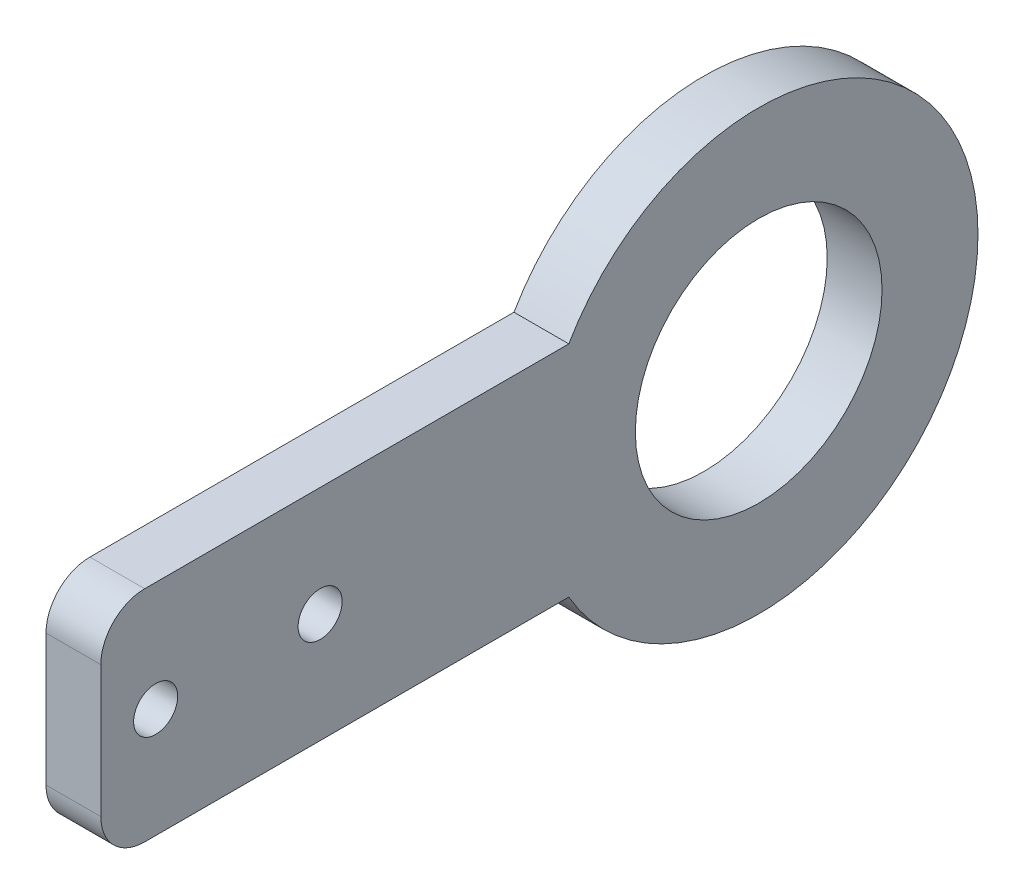
SolidWorks part; units mm, degrees
material "5052-O"
ref_plane "Front Plane" through (0, 0, 0) normal (0, 0, 1) x (1, 0, 0)
ref_plane "Top Plane" through (0, 0, 0) normal (0, 1, 0) x (1, 0, 0)
ref_plane "Right Plane" through (0, 0, 0) normal (1, 0, 0) x (0, 0, -1)
sketch "Sketch1" plane through (0, 0, 0) normal (1, 0, 0) x (0, 0, -1)
  line L1 (-44.45, -12.7) -> (44.45, -12.7)
  line L2 (-44.45, -12.7) -> (-44.45, 12.7)
  line L3 (-44.45, 12.7) -> (44.45, 12.7)
  line L4 (44.45, -12.7) -> (44.45, 12.7)
  line L5 (-44.45, -12.7) -> (44.45, 12.7) construction
  line L6 (-44.45, 12.7) -> (44.45, -12.7) construction
  point P0 (0, 0)
  dimension "D1" = 25.4
  dimension "D2" = 88.9
extrude "Boss-Extrude1" add sketch "Sketch1" along normal mid plane 6.35
fillet "Fillet1" radius 12.7 2 edges at (0, -12.7, -44.45) (0, 12.7, -44.45)
hole_wizard "#10 Clearance Hole1" positions "Sketch3" profile "Sketch5" hole size "#10" standard "ANSI Inch" end condition through all
sketch "Sketch3" plane through (3.175, 6.2729, 168.827) normal (1, 0, 0) x (0, 0, -1)
  line L0 (124.377, 6.4271) -> (124.377, -18.9729) construction
  point P0 (149.777, -6.2729)
  point P3 (130.727, -6.2729)
  point P8 (124.377, -6.2729)
  dimension "D1" = 19.05
  dimension "D2" = 6.35
sketch "Sketch5" plane through (3.175, 0, 19.05) normal (0, 1, 0) x (0, 0, -1)
  line L0 (0, 0) -> (0, 6.35)
  line L1 (0, 6.35) -> (2.5527, 6.35)
  line L2 (2.5527, 6.35) -> (2.5527, 0)
  line L5 (2.5527, 0) -> (0, 0)
  line L11 (0, -6.35) -> (0, 107.95) construction
  dimension "Thru Hole Dia." = 5.1054
  dimension "Thru Hole Depth" = 6.35
fillet "Fillet2" radius 5.08 2 edges at (0, -12.7, 44.45) (0, 12.7, 44.45)
sketch "Sketch6" plane through (3.175, 0, 0) normal (1, 0, 0) x (0, 0, -1)
  circle A0 centre (31.75, 0) radius 25.4
  arc A1 (44.45, 0) -> (31.75, 12.7) centre (31.75, 0) ccw construction
  point P5 (0, 0)
  dimension "D1" = 50.8
extrude "Boss-Extrude2" add sketch "Sketch6" against normal up to surface (6.35 mm away) up to face at (-3.175, 0, 16.4973)
sketch "Sketch7" plane through (3.175, 0, 0) normal (1, 0, 0) x (0, 0, -1)
  circle A0 centre (31.75, 0) radius 14.2875
  arc A2 (9.753, -12.7) -> (9.753, 12.7) centre (31.75, 0) ccw construction
  dimension "D1" = 28.575
extrude "Cut-Extrude1" cut sketch "Sketch7" against normal through all
